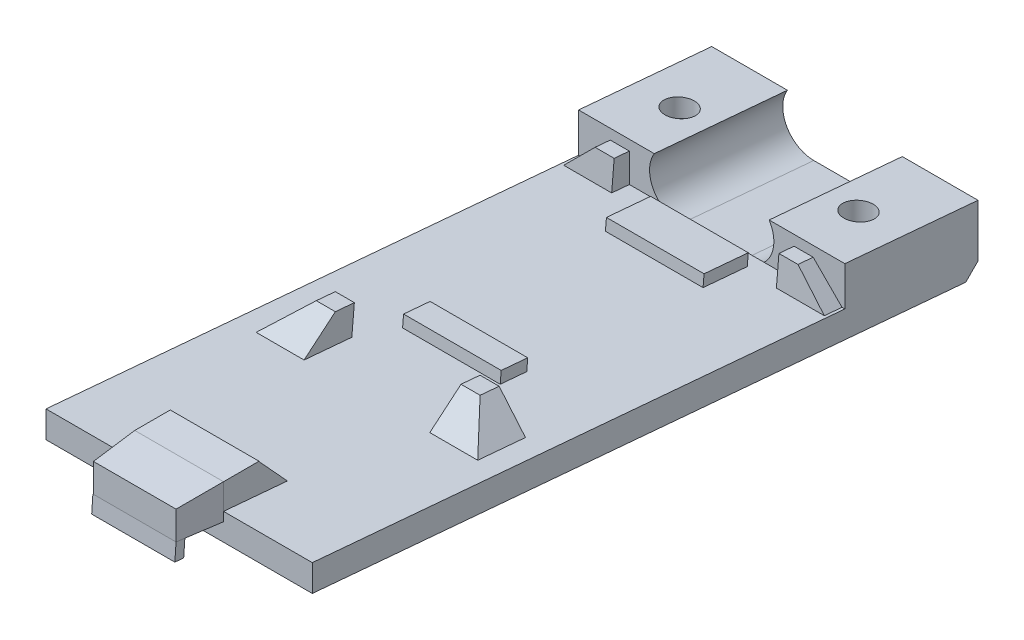
SolidWorks part; units mm, degrees
ref_plane "Front Plane" through (0, 0, 0) normal (0, 0, 1) x (1, 0, 0)
ref_plane "Top Plane" through (0, 0, 0) normal (0, 1, 0) x (1, 0, 0)
ref_plane "Right Plane" through (0, 0, 0) normal (1, 0, 0) x (0, 0, -1)
sketch "Sketch1" plane through (0, -17.7206, 1.5504) normal (0, -0.9962, 0.0872) x (1, 0, 0)
  line L0 (148.7923, -105.9785) -> (148.7923, -105.4618) construction
  line L1 (178.7923, -105.9785) -> (148.7923, -105.9785)
  line L2 (178.7923, -105.9785) -> (178.7923, -30.8227)
  line L3 (178.7923, -30.8227) -> (148.7923, -30.8227)
  line L4 (148.7923, -105.9785) -> (148.7923, -30.8227)
  line L5 (148.7923, -105.9785) -> (136.798, -105.9785) construction
sketch "Sketch2" plane through (148.7923, 0, 0) normal (1, 0, 0) x (0, 0, -1)
  line L0 (89.1551, -22.6448) -> (104.1551, -23.9572)
  line L9 (89.1551, -18.228) -> (89.1551, -22.6448)
  line L10 (89.1551, -22.6448) -> (83.4589, -22.1465)
  line L11 (29.1551, -14.6852) -> (29.1551, -20.407)
  line L12 (29.1551, -20.407) -> (102.7758, -26.8479)
  line L16 (89.1551, -18.228) -> (89.1551, -22.6448)
  line L17 (89.1551, -22.6448) -> (83.4589, -22.1465)
  line L18 (29.1551, -17.3955) -> (29.1551, -20.407)
  line L19 (29.1551, -20.407) -> (102.7758, -26.8479)
  line L45 (104.1551, -25.4686) -> (104.1551, -19.5404)
  line L46 (104.1551, -25.4686) -> (104.1551, -19.5404)
  line L47 (104.1551, -19.5404) -> (89.1551, -18.228)
  line L48 (104.1551, -19.5404) -> (89.1551, -18.228)
  line L49 (102.7758, -26.8479) -> (104.1551, -25.4686)
  line L50 (102.7758, -26.8479) -> (104.1551, -25.4686)
  line L52 (83.4589, -22.1465) -> (29.1551, -14.6852)
  line L53 (83.4589, -22.1465) -> (29.1551, -17.3955)
  line L54 (29.1551, -20.407) -> (29.1551, -14.6852) construction
  line M9 (104.1551, -25.4686) -> (104.1551, -19.5404)
  line M12 (89.1551, -22.6448) -> (83.4589, -22.1465)
  line M13 (29.1551, -14.6852) -> (29.1551, -20.407)
  line M14 (29.1551, -20.407) -> (102.7758, -26.8479)
  line M15 (102.7758, -26.8479) -> (104.1551, -25.4686)
  dimension "D1" = 0
extrude "Boss-Extrude2" add sketch "Sketch2" along normal up to surface (30 mm away) contours L0 M12 M13 M14 M15 M9 | L17 L53 L18 L19 L50 L46 L48 L16
ref_plane "Plane1" through (0, -9.2366, -105.5752) normal (0, -0.0872, -0.9962) x (-1, 0, 0)
sketch "Sketch4" plane through (0, -9.2366, -105.5752) normal (0, -0.0872, -0.9962) x (-1, 0, 0)
  line L0 (-167.2923, -12.2383) -> (-160.2923, -12.2383) construction
  line L1 (-167.2923, -8.7383) -> (-160.2923, -8.7383)
  line L2 (-167.2923, -15.7383) -> (-160.2923, -15.7383)
  arc A0 (-167.2923, -8.7383) -> (-167.2923, -15.7383) centre (-167.2923, -12.2383) ccw
  arc A1 (-160.2923, -15.7383) -> (-160.2923, -8.7383) centre (-160.2923, -12.2383) ccw
  arc A2 (-157.3212, -10.3883) -> (-160.2923, -8.7383) centre (-160.2923, -12.2383) ccw construction
  arc A3 (-167.2923, -8.7383) -> (-170.2634, -10.3883) centre (-167.2923, -12.2383) ccw construction
  point P2 (-163.7923, -12.2383)
extrude "Cut-Extrude1" cut sketch "Sketch4" against normal up to surface (15.7183 mm away)
sketch "Sketch6" plane through (0, -14.5, 0) normal (0, -1, 0) x (-1, 0, 0)
  circle A0 centre (-173.8692, 95.6135) radius 2.85
  circle A1 centre (-153.7153, 95.6135) radius 2.85
  dimension "D1" = 5.7
extrude "Cut-Extrude2" cut sketch "Sketch6" along normal through all from offset 7
sketch "Sketch7" plane through (0, -4.5, 0) normal (0, 1, 0) x (1, 0, 0)
  circle A0 centre (173.8692, 95.6135) radius 1.65
  circle A1 centre (153.7153, 95.6135) radius 1.65
  circle A2 centre (153.7153, 95.6135) radius 1.65 construction
  dimension "D1" = 3.3
extrude "Cut-Extrude3" cut sketch "Sketch7" against normal through all
sketch "Sketch9" plane through (0, 0, -29.1551) normal (0, 0, 1) x (1, 0, 0)
  line L0 (178.7923, -20.407) -> (148.7923, -20.407) construction
  line L1 (168.7923, -20.407) -> (158.7923, -20.407)
  line L2 (168.7923, -20.407) -> (168.7923, -14.5)
  line L3 (168.7923, -14.5) -> (158.7923, -14.5)
  line L4 (158.7923, -20.407) -> (158.7923, -14.5)
  line L5 (178.7923, -17.3955) -> (148.7923, -17.3955) construction
  line L6 (148.7923, -14.5) -> (178.7923, -14.5) construction
  point P8 (163.7923, -17.3955)
  point P9 (163.7923, -14.5)
  dimension "D1" = 10
extrude "Boss-Extrude4" add sketch "Sketch9" against normal blind 4
sketch "Sketch10" plane through (0, 0, -29.1551) normal (0, 0, 1) x (1, 0, 0)
  line L0 (178.7923, -20.407) -> (148.7923, -20.407) construction
  line L1 (168.7923, -14.5) -> (158.7923, -14.5)
  line L2 (168.7923, -14.5) -> (168.7923, -17.3955)
  line L3 (168.7923, -17.3955) -> (158.7923, -17.3955)
  line L4 (158.7923, -14.5) -> (158.7923, -17.3955)
  line L5 (168.7923, -14.5) -> (158.7923, -14.5)
  line L6 (168.7923, -14.5) -> (168.7923, -18.407)
  line L7 (168.7923, -18.407) -> (158.7923, -18.407)
  line L8 (158.7923, -14.5) -> (158.7923, -18.407)
  line M7 (168.7923, -17.3955) -> (168.7923, -14.5)
  line M8 (168.7923, -14.5) -> (158.7923, -14.5)
  line M9 (158.7923, -14.5) -> (158.7923, -17.3955)
  dimension "D1" = 2
extrude "Boss-Extrude5" add sketch "Sketch10" along normal blind 5 draft 4 contours L3 M7 M8 M9 | L3 L8 L7 L6
fillet "Fillet1" radius 3.5 1 edges at (163.7923, -17.7455, -33.1551)
sketch "Sketch11" plane through (0, -21.5, 0) normal (0, -1, 0) x (1, 0, 0)
  line L0 (171.5454, -97.2635) -> (176.193, -97.2635)
  line L1 (171.5454, -93.9635) -> (176.193, -93.9635)
  circle A1 centre (173.8692, -95.6135) radius 2.85 construction
  arc A3 (176.193, -97.2635) -> (176.193, -93.9635) centre (173.8692, -95.6135) ccw
  arc A4 (171.5454, -97.2635) -> (171.5454, -93.9635) centre (173.8692, -95.6135) cw
  circle A5 centre (173.8692, -95.6135) radius 1.65 construction
  point P3 (173.8692, -97.2635)
  point P8 (173.8692, -93.9635)
extrude "Cut-Extrude4" cut sketch "Sketch11" against normal blind 0.25
sketch "Sketch12" plane through (0, -21.25, 0) normal (0, -1, 0) x (1, 0, 0)
  line L0 (175.5192, -93.9635) -> (175.5192, -97.2635)
  line L1 (172.2192, -93.9635) -> (172.2192, -97.2635)
  line L2 (171.5454, -97.2635) -> (173.8692, -97.2635) construction
  line L3 (175.5192, -97.2635) -> (172.2192, -97.2635)
  line L4 (175.5192, -93.9635) -> (172.2192, -93.9635)
  circle A2 centre (173.8692, -95.6135) radius 1.65 construction
  arc A3 (173.8692, -93.9635) -> (173.8692, -97.2635) centre (173.8692, -95.6135) ccw construction
  point P3 (175.5192, -95.6135)
  point P6 (172.2192, -95.6135)
extrude "Cut-Extrude5" cut sketch "Sketch12" against normal blind 0.25
ref_plane "Plane2" through (163.7923, 0, 0) normal (1, 0, 0) x (0, 0, -1)
mirror "Mirror1" about plane through (163.7923, 0, 0) normal (1, 0, 0) of "Cut-Extrude4", "Cut-Extrude5"
sketch "Sketch13" plane through (0, -14.732, 1.2889) normal (0, 0.9962, -0.0872) x (1, 0, 0)
  line L1 (170.8723, 55.1977) -> (172.8723, 55.1977)
  line L2 (170.8723, 55.1977) -> (170.8723, 57.1977)
  line L3 (170.8723, 57.1977) -> (172.8723, 57.1977)
  line L4 (172.8723, 55.1977) -> (172.8723, 57.1977)
  line L5 (155.7123, 56.9977) -> (171.8723, 56.9977) construction
  line L6 (173.0723, 58.1977) -> (173.0723, 89.1577) construction
  line L7 (173.0723, 88.7894) -> (175.0723, 88.7894)
  line L8 (173.0723, 88.7894) -> (173.0723, 90.7894)
  line L9 (173.0723, 90.7894) -> (175.0723, 90.7894)
  line L10 (175.0723, 88.7894) -> (175.0723, 90.7894)
  line L11 (169.6897, 90.7894) -> (178.7923, 90.7894) construction
  dimension "D1" = 0.2
  dimension "D2" = 2
  dimension "D3" = 2
  dimension "D4" = 1
  dimension "D5" = 2
  dimension "D6" = 2
extrude "Boss-Extrude6" add sketch "Sketch13" along normal blind 3.25
chamfer "Chamfer1" distance 3.4 angle 45 3 edges at (171.8723, -19.5428, -53.6988) (172.8723, -19.63, -54.695) (175.0723, -22.5577, -88.1589)
mirror "Mirror2" about plane through (163.7923, 0, 0) normal (1, 0, 0) of "Chamfer1", "Boss-Extrude6"
sketch "Sketch14" plane through (0, -16.2886, 1.139) normal (0, -0.9976, 0.0698) x (1, 0, 0)
  line L0 (159.1419, -25.3559) -> (158.7923, -30.3681) construction
  line L1 (168.4426, -25.3559) -> (159.0721, -25.3559)
  line L2 (168.4426, -25.3559) -> (168.4426, -26.3559)
  line L3 (168.4426, -26.3559) -> (159.0721, -26.3559)
  line L4 (159.0721, -25.3559) -> (159.0721, -26.3559)
  dimension "D1" = 1
extrude "Boss-Extrude7" add sketch "Sketch14" along normal up to surface (1.9052 mm away)
sketch "Sketch17" plane through (0, -14.732, 1.2889) normal (0, 0.9962, -0.0872) x (1, 0, 0)
  line L0 (163.7923, 37.7827) -> (163.7923, 90.7894) construction
  line L1 (158.7923, 37.7827) -> (168.7923, 37.7827) construction
  line L2 (157.8949, 90.7894) -> (169.6897, 90.7894) construction
  line L4 (158.2923, 84.2894) -> (169.2923, 84.2894)
  line L5 (158.2923, 84.2894) -> (158.2923, 89.2894)
  line L6 (158.2923, 89.2894) -> (169.2923, 89.2894)
  line L7 (169.2923, 84.2894) -> (169.2923, 89.2894)
  line L8 (164.9723, 61.3477) -> (167.9723, 61.3477) construction
  line L9 (158.2923, 61.3477) -> (169.2923, 61.3477)
  line L10 (158.2923, 61.3477) -> (158.2923, 64.3477)
  line L11 (158.2923, 64.3477) -> (169.2923, 64.3477)
  line L12 (169.2923, 61.3477) -> (169.2923, 64.3477)
  point P10 (163.7923, 89.2894)
  dimension "D1" = 11
  dimension "D2" = 5
  dimension "D3" = 3
  dimension "D4" = 1.5
extrude "Boss-Extrude8" add sketch "Sketch17" along normal blind 1.3
